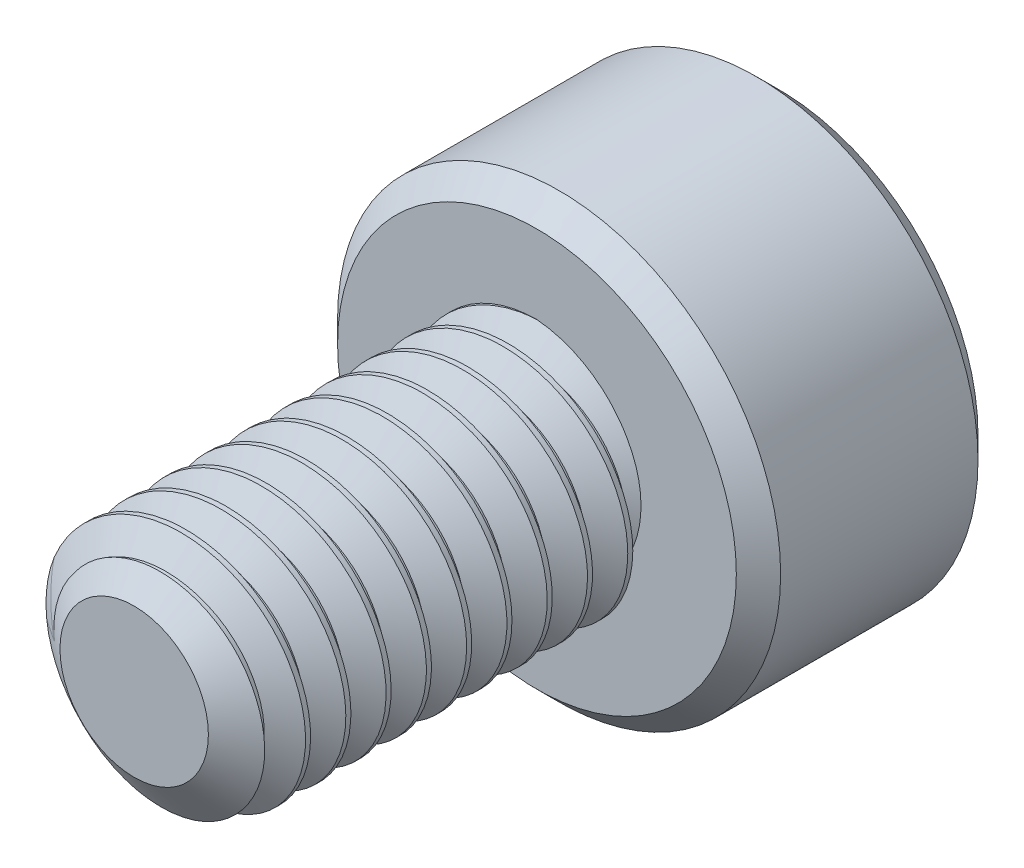
SolidWorks part; units mm, degrees
other "DetailItem1"
ref_plane "Front Plane" through (0, 0, 0) normal (0, 0, 1) x (1, 0, 0)
ref_plane "Top Plane" through (0, 0, 0) normal (0, 1, 0) x (1, 0, 0)
ref_plane "Right Plane" through (0, 0, 0) normal (1, 0, 0) x (0, 0, -1)
sketch "Sketch1" plane through (0, 0, 0) normal (0, 0, 1) x (1, 0, 0)
  circle A0 centre (0, 0) radius 1.5
  dimension "OD" = 3
extrude "Extrude1" add sketch "Sketch1" against normal blind 5
sketch "Sketch2" plane through (0, 0, 0) normal (0, 0, 1) x (1, 0, 0)
  circle A0 centre (0, 0) radius 1.5 construction
  circle A1 centre (0, 0) radius 1.5
curve "Helix/Spiral1" pitch 0.5 height 5.5 radius 1.5 centre (0, 0, 0) axis (0, 0, -1) start towards (0, 1, 0) parameters "pitch"=0.5
sketch "Sketch3" plane through (0, 0, 0) normal (1, 0, 0) x (0, 0, -1)
  line L0 (-0.4375, 1.5) -> (-0.25, 1.1752)
  line L1 (-0.25, 1.1752) -> (-0.1875, 1.1752)
  line L2 (-0.1875, 1.1752) -> (0, 1.5)
  line L3 (-0.4375, 1.5) -> (0, 1.5)
  line L4 (-0.2187, 1.5) -> (-0.2188, 1.1752) construction
  line L5 (-0.3438, 1.3376) -> (-0.0938, 1.3376) construction
  line L6 (0, 1.5) -> (0, -1.5) construction
  dimension "D1" = 0.0625
  dimension "D2" = 0.25
  dimension "D3" = 60
sweep "Cut-Sweep1" cut profiles "Sketch3" path "Helix/Spiral1"
sketch "Sketch4" plane through (0, 0, 0) normal (1, 0, 0) x (0, 0, -1)
  line L0 (0.4053, 1.5) -> (0, 0.9212)
  line L1 (0, 0.9212) -> (0, 1.5)
  line L2 (0.4053, 1.5) -> (0, 1.5)
  line L3 (-0.4375, 1.5) -> (0, 1.5) construction
  line L4 (0, 0) -> (7.0209, 0) construction
  dimension "D1" = 55
  dimension "D2" = 0.254
revolve "Cut-Revolve1" cut sketch "Sketch4" angle 360 about L4
sketch "Sketch6" plane through (0, 0, -5) normal (0, 0, -1) x (-1, 0, 0)
  circle A0 centre (0, 0) radius 2.75
  dimension "head dia" = 5.5
extrude "Extrude2" add sketch "Sketch6" along normal blind 3
sketch "Sketch7" plane through (0, 0, -8) normal (0, 0, -1) x (-1, 0, 0)
  line L1 (0, 1.4434) -> (-1.25, 0.7217)
  line L2 (-1.25, 0.7217) -> (-1.25, -0.7217)
  line L3 (-1.25, -0.7217) -> (0, -1.4434)
  line L4 (0, -1.4434) -> (1.25, -0.7217)
  line L5 (1.25, -0.7217) -> (1.25, 0.7217)
  line L6 (1.25, 0.7217) -> (0, 1.4434)
  circle A0 centre (0, 0) radius 1.25 construction
  dimension "hex dia" = 2.5
extrude "Cut-Extrude1" cut sketch "Sketch7" against normal blind 1.875
sketch "Sketch8" plane through (0, 0, -8) normal (0, 0, -1) x (-1, 0, 0)
  circle A0 centre (0, 0) radius 1.4434
extrude "Cut-Extrude2" cut sketch "Sketch8" against normal through all draft 45
chamfer "Chamfer1" distance 0.275 angle 45 2 edges at (-2.75, 0, -8) (-2.75, 0, -5)
sketch "Sketch10" plane through (0, 0, -5) normal (0, 0, 1) x (1, 0, 0)
  circle A1 centre (0, 0) radius 1.5
  circle A2 centre (0, 0) radius 1.5
  dimension "D1" = 0
ref_plane "Plane1" through (0, 0, 0) normal (0, 0, 1) x (1, 0, 0)
extrude "partial thread" [suppressed] add sketch "Sketch10" along normal up to surface (4 mm away) separate body up to plane "Plane1"
chamfer "Chamfer2" [suppressed] distance 0.06 angle 45
combine bodies "Combine1" [suppressed] operation type add bodies to combine 107 108
sketch "Sketch9" plane through (0, 0, 0) normal (1, 0, 0) x (0, 0, -1)
  line L0 (0, 1.5) -> (0, -1.5) construction
  line L1 (1.25, 1.5) -> (1.25, -1.5) construction
  dimension "D1" = 1.25
equation "\"D3@Helix/Spiral1\" = \"screw length@Extrude1\"+\"pitch@Helix/Spiral1\""
equation "\"D1@Sketch3\" = \"pitch@Helix/Spiral1\"*.125"
equation "\"D2@Sketch3\" = \"pitch@Helix/Spiral1\"*.5"
equation "\"D1@Cut-Extrude1\" = \"hex dia@Sketch7\"*.75"
equation "\"D1@Chamfer1\" = \"head dia@Sketch6\"*.05"
equation "\"D1@Sketch9\" = \"pitch@Helix/Spiral1\"*2.5"
equation "\"D1@Chamfer2\"=\"OD@Sketch1\"*.02"
